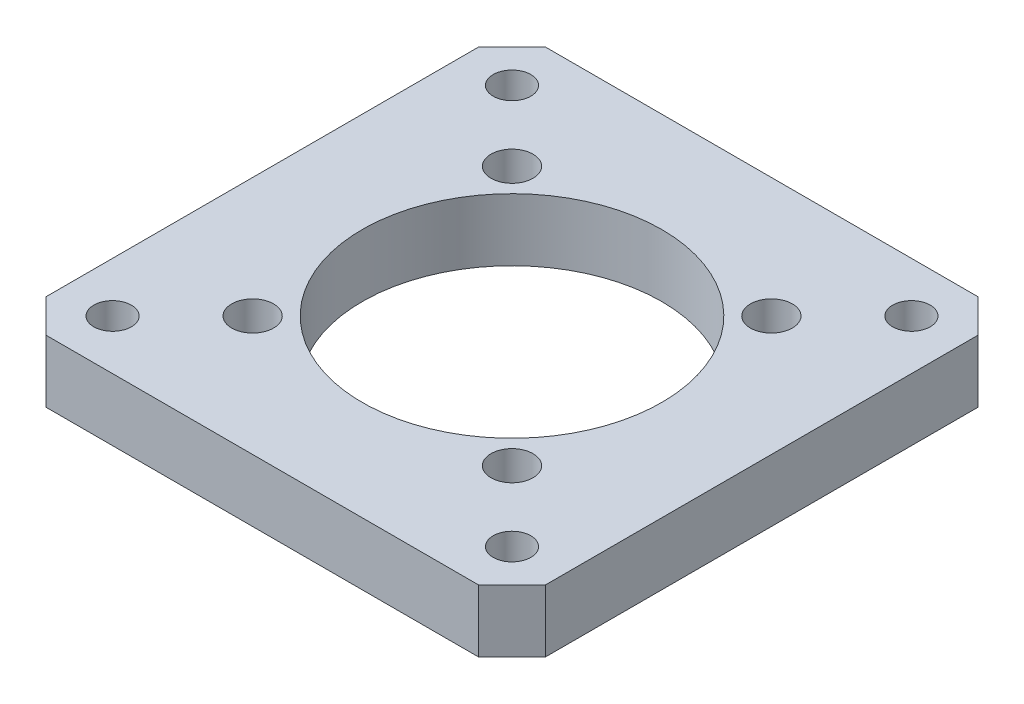
SolidWorks part; units mm, degrees
material "Alum Plate"
ref_plane "Front Plane" through (0, 0, 0) normal (0, 0, 1) x (1, 0, 0)
ref_plane "Top Plane" through (0, 0, 0) normal (0, 1, 0) x (1, 0, 0)
ref_plane "Right Plane" through (0, 0, 0) normal (1, 0, 0) x (0, 0, -1)
other "Bounding Box"
ref_plane "Default Plane" through (0, 2.286, 19.05) normal (0, -1, 0) x (-1, 0, 0)
sketch "Sketch1" plane through (0, 0, 0) normal (0, 1, 0) x (1, 0, 0)
  line L1 (-19.05, 19.05) -> (19.05, 19.05)
  line L2 (-19.05, 19.05) -> (-19.05, -19.05)
  line L3 (-19.05, -19.05) -> (19.05, -19.05)
  line L4 (19.05, 19.05) -> (19.05, -19.05)
  line L5 (-19.05, 19.05) -> (19.05, -19.05) construction
  line L6 (-19.05, -19.05) -> (19.05, 19.05) construction
  circle A0 centre (0, 0) radius 11.43
  point P0 (0, 0)
  dimension "D2" = 22.86
  dimension "D1" = 38.1
extrude "Boss-Extrude1" add sketch "Sketch1" along normal blind 4.7625
sketch "Sketch2" plane through (0, 4.7625, 0) normal (0, 1, 0) x (1, 0, 0)
  line L0 (0, 0) -> (9.8962, 9.8962) construction
  line L1 (0, 0) -> (15.24, 15.24) construction
  line L2 (15.24, 15.24) -> (19.05, 15.24) construction
  line L3 (19.05, -19.05) -> (19.05, 19.05) construction
  line L4 (15.24, 15.24) -> (15.24, 19.05) construction
  line L5 (19.05, 19.05) -> (-19.05, 19.05) construction
  circle A0 centre (9.8962, 9.8962) radius 1.6002
  circle A1 centre (15.24, 15.24) radius 1.4351
  point P12 (9.8962, 9.8962)
  dimension "D1" = 3.2004
  dimension "D3" = 2.8702
  dimension "D2" = 13.9954
  dimension "D4" = 3.81
extrude "Cut-Extrude1" cut sketch "Sketch2" against normal through all
pattern_circular "CirPattern1" count 4 over 360 about axis through (0, 4.7625, 0) along (0, -1, 0) of "Cut-Extrude1"
chamfer "Chamfer1" distance 2.54 angle 45 4 edges at (-19.05, 2.3813, 19.05) (19.05, 2.3813, 19.05) (19.05, 2.3813, -19.05) (-19.05, 2.3813, -19.05)
equation "\"Unit Measure\"= \"BoundingVolume\" / \"Thickness\"'in^2"
